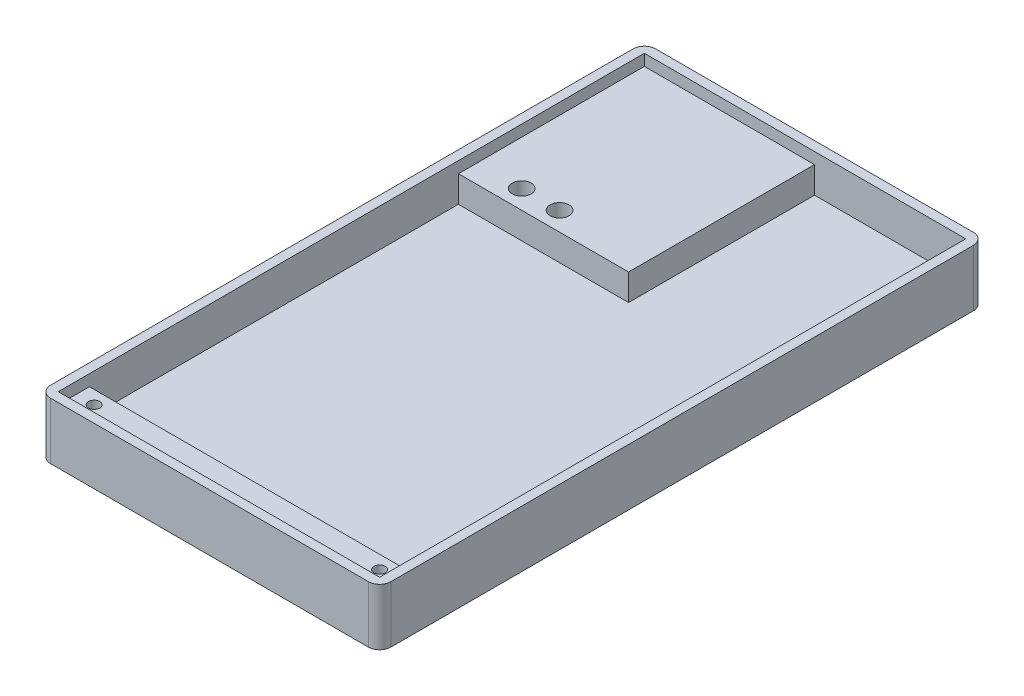
SolidWorks part; units mm, degrees
ref_plane "Front Plane" through (0, 0, 0) normal (0, 0, 1) x (1, 0, 0)
ref_plane "Top Plane" through (0, 0, 0) normal (0, 1, 0) x (1, 0, 0)
ref_plane "Right Plane" through (0, 0, 0) normal (1, 0, 0) x (0, 0, -1)
sketch "Sketch1" plane through (0, 0, 0) normal (0, 1, 0) x (1, 0, 0)
  line L1 (-43.2731, 51.8059) -> (46.7269, 51.8059)
  line L2 (-43.2731, 51.8059) -> (-43.2731, -108.1941)
  line L3 (-43.2731, -108.1941) -> (46.7269, -108.1941)
  line L4 (46.7269, 51.8059) -> (46.7269, -108.1941)
  dimension "D1" = 90
  dimension "D2" = 160
extrude "Boss-Extrude1" add sketch "Sketch1" along normal blind 5 contours L1 L4 L3 L2
sketch "Sketch2" plane through (0, 5, 0) normal (0, 1, 0) x (1, 0, 0)
  line L1 (-43.2731, 51.8059) -> (46.7269, 51.8059)
  line L2 (-43.2731, 51.8059) -> (-43.2731, -108.1941)
  line L3 (-43.2731, -108.1941) -> (46.7269, -108.1941)
  line L4 (46.7269, 51.8059) -> (46.7269, -108.1941)
  line L5 (-40.7731, 49.3059) -> (44.2269, 49.3059)
  line L6 (-40.7731, 49.3059) -> (-40.7731, -105.6941)
  line L7 (-40.7731, -105.6941) -> (44.2269, -105.6941)
  line L8 (44.2269, 49.3059) -> (44.2269, -105.6941)
  dimension "D1" = 85
  dimension "D2" = 2.5
  dimension "D3" = 155
  dimension "D4" = 2.5
extrude "Boss-Extrude2" add sketch "Sketch2" along normal blind 10
sketch "Sketch3" plane through (0, 5, 0) normal (0, 1, 0) x (1, 0, 0)
  line L0 (44.2269, -105.6941) -> (44.2269, 49.3059) construction
  line L1 (-40.7731, -105.6941) -> (44.2269, -105.6941)
  line L2 (-40.7731, -105.6941) -> (-40.7731, -97.4441)
  line L3 (-40.7731, -97.4441) -> (44.2269, -97.4441)
  line L4 (44.2269, -105.6941) -> (44.2269, -97.4441)
  circle A0 centre (-36.0231, -100.9441) radius 1.5
  circle A1 centre (39.4769, -100.9441) radius 1.5
  point P13 (-29.9962, -77.8679)
  dimension "D4" = 3
  dimension "D7" = 3
  dimension "D1" = 8.25
  dimension "D2" = 4.75
  dimension "D3" = 4.75
  dimension "D5" = 4.75
  dimension "D6" = 4.75
extrude "Boss-Extrude3" add sketch "Sketch3" along normal blind 7
sketch "Sketch4" plane through (0, 5, 0) normal (0, 1, 0) x (1, 0, 0)
  line L0 (-40.7731, 49.3059) -> (-40.7731, -97.4441) construction
  line L1 (-40.7731, 10.1309) -> (4.2269, 10.1309)
  line L2 (-40.7731, 10.1309) -> (-40.7731, 0.1309)
  line L3 (-40.7731, 0.1309) -> (4.2269, 0.1309)
  line L4 (4.2269, 10.1309) -> (4.2269, 0.1309)
  line L5 (44.2269, 49.3059) -> (-40.7731, 49.3059) construction
  line L7 (4.2269, 10.1309) -> (-40.7731, 10.1309)
  line L8 (4.2269, 10.1309) -> (4.2269, 49.3059)
  line L9 (4.2269, 49.3059) -> (-40.7731, 49.3059)
  line L10 (-40.7731, 10.1309) -> (-40.7731, 49.3059)
  circle A0 centre (-29.0231, 5.1309) radius 2.5
  circle A1 centre (-19.0231, 5.1309) radius 2.5
  line M6 (-40.7731, 49.3059) -> (-40.7731, -97.4441)
  line M9 (44.2269, 49.3059) -> (-40.7731, 49.3059)
  dimension "D3" = 5
  dimension "D4" = 5
  dimension "D1" = 11.75
  dimension "D2" = 21.75
  dimension "D5" = 10
  dimension "D6" = 5
  dimension "D7" = 5
  dimension "D8" = 44.175
  dimension "D9" = 45
extrude "Boss-Extrude4" add sketch "Sketch4" along normal up to surface (7 mm away) contours L1 L8 M9 M6 | L4 L1 L3 A1 A0 M6 region at (-18.2731, 5, -29.7184) region at (-18.2731, 5, -9.6699) up to face at (1.7269, 12, 101.5691)
fillet "Fillet1" radius 3 4 edges at (-43.2731, 7.5, -51.8059) (46.7269, 7.5, -51.8059) (46.7269, 7.5, 108.1941) (-43.2731, 7.5, 108.1941)
sketch "Sketch5" plane through (0, 5, 0) normal (0, 1, 0) x (1, 0, 0)
  circle A0 centre (-19.0231, 5.1309) radius 2.5
  circle A1 centre (-29.0231, 5.1309) radius 2.5593
  circle A2 centre (-36.0231, -100.9441) radius 1.5
  circle A3 centre (39.4769, -100.9441) radius 1.5
extrude "Cut-Extrude1" cut sketch "Sketch5" against normal through all
